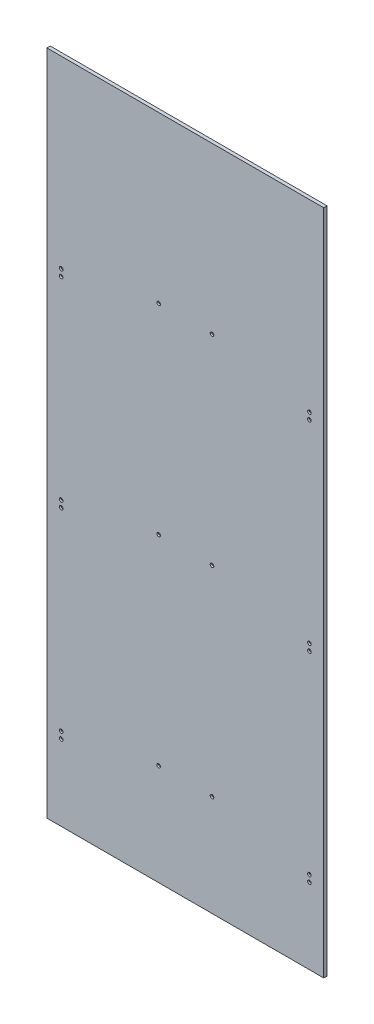
SolidWorks part; units mm, degrees
material "Pine"
ref_plane "Front Plane" through (0, 0, 0) normal (0, 0, 1) x (1, 0, 0)
ref_plane "Top Plane" through (0, 0, 0) normal (0, 1, 0) x (1, 0, 0)
ref_plane "Right Plane" through (0, 0, 0) normal (1, 0, 0) x (0, 0, -1)
sketch "Sketch1" plane through (0, 0, 0) normal (0, 0, 1) x (1, 0, 0)
  line L1 (-481.584, 1513.4749) -> (501.65, 1513.4749)
  line L2 (-481.584, 1513.4749) -> (-481.584, -874.1251)
  line L3 (-481.584, -874.1251) -> (501.65, -874.1251)
  line L4 (501.65, 1513.4749) -> (501.65, -874.1251)
  dimension "D1" = 983.234
  dimension "D2" = 2387.6
extrude "Boss-Extrude1" add sketch "Sketch1" along normal blind 11.9062
hole_wizard "CSK for 1/4 Flat Head Machine Screw1" positions "Sketch2" profile "Sketch3" countersink size "1/4" standard "ANSI Inch" end condition through all
sketch "Sketch2" plane through (0, 0, 11.9062) normal (0, 0, 1) x (1, 0, 0)
  line L0 (-481.584, 1513.4749) -> (-481.584, -874.1251) construction
  line L1 (-481.584, -874.1251) -> (501.65, -874.1251) construction
  line L3 (10.033, -874.1251) -> (10.033, 1867.2959) construction
  line L5 (501.65, -874.1251) -> (501.65, 1513.4749) construction
  point P0 (-430.784, -562.9751)
  point P2 (-430.784, -586.7876)
  point P4 (-84.709, -496.3001)
  point P6 (104.775, -496.3001)
  point P8 (450.85, -586.7876)
  point P10 (450.85, -562.9751)
  point P12 (450.85, 148.2249)
  point P14 (450.85, 124.4124)
  point P16 (104.775, 214.8999)
  point P18 (-84.709, 214.8999)
  point P20 (-430.784, 124.4124)
  point P22 (-430.784, 148.2249)
  point P24 (-430.784, 859.4249)
  point P26 (-430.784, 835.6124)
  point P28 (-84.709, 926.0999)
  point P30 (104.775, 926.0999)
  point P32 (450.85, 835.6124)
  point P34 (450.85, 859.4249)
  point P71 (0, 0)
  dimension "D1" = 50.8
  dimension "D2" = 50.8
  dimension "D3" = 396.875
  dimension "D4" = 94.742
  dimension "D5" = 50.8
  dimension "D6" = 50.8
  dimension "D7" = 311.15
  dimension "D8" = 287.3375
  dimension "D9" = 377.825
  dimension "D10" = 1089.025
  dimension "D11" = 998.5375
  dimension "D12" = 1022.35
  dimension "D13" = 1733.55
  dimension "D14" = 1709.7375
  dimension "D15" = 1800.225
  dimension "D17" = 94.742
  dimension "D18" = 94.742
sketch "Sketch3" plane through (-430.784, -562.9751, 11.9062) normal (1, 0, 0) x (0, -1, 0)
  line L0 (0, 0) -> (0, 11.9062)
  line L1 (0, 11.9062) -> (3.3782, 11.9062)
  line L2 (3.3782, 11.9062) -> (3.3782, 3.5209)
  line L3 (3.3782, 3.5209) -> (6.4389, 0)
  line L5 (6.4389, 0) -> (0, 0)
  line L6 (-3.3782, 3.5209) -> (-6.4389, 0) construction
  line L11 (0, -6.35) -> (0, 107.95) construction
  dimension "Thru Hole Dia." = 6.7564
  dimension "Thru Hole Depth" = 11.9062
  dimension "Near C'Sink Dia." = 12.8778
  dimension "Near C'Sink Angle" = 82
sketch "Sketch4" plane through (0, 0, 11.9062) normal (0, 0, 1) x (1, 0, 0)
  line L0 (501.65, -874.1251) -> (501.65, 1513.4749) construction
  line L1 (-481.584, -874.1251) -> (501.65, -874.1251)
  line L2 (-481.584, -874.1251) -> (-481.584, -855.8689)
  line L3 (-481.584, -855.8689) -> (501.65, -855.8689)
  line L4 (501.65, -874.1251) -> (501.65, -855.8689)
  dimension "D1" = 18.2562
extrude "Cut-Extrude1" cut sketch "Sketch4" against normal through all
